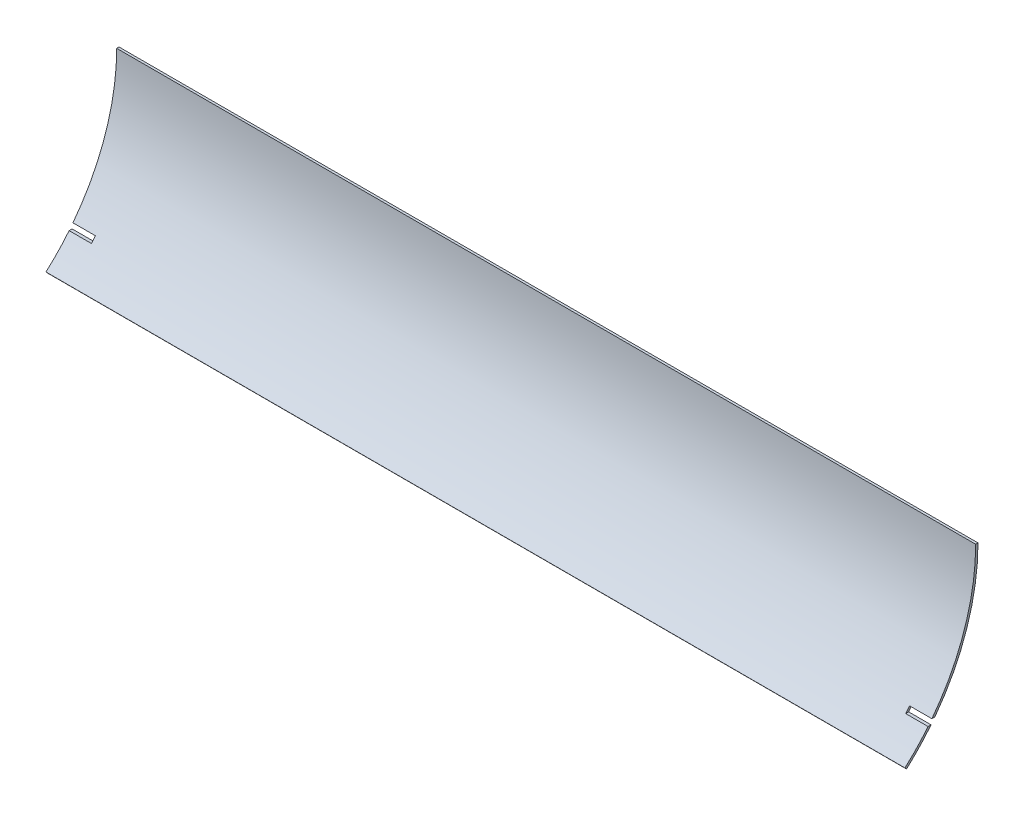
SolidWorks part; units mm, degrees
ref_plane "Front Plane" through (0, 0, 0) normal (0, 0, 1) x (1, 0, 0)
ref_plane "Top Plane" through (0, 0, 0) normal (0, 1, 0) x (1, 0, 0)
ref_plane "Right Plane" through (0, 0, 0) normal (1, 0, 0) x (0, 0, -1)
sketch "Sketch2" plane through (0, 0, 0) normal (1, 0, 0) x (0, 0, -1)
  arc A1 (97.053, -108.2878) -> (145.415, 0) centre (0, 0) ccw
  dimension "D1" = 145.415
extrude "Extrude-Thin1" add sketch "Sketch2" along normal blind 584.2 thin thin type mid plane wall 1.5875
sketch "Sketch3" plane through (0, 0, 0) normal (0, 0, 1) x (1, 0, 0)
  line L0 (0, -91.1867) -> (15.24, -91.1867)
  line L1 (0, 0) -> (0, -107.6967) construction
  line L2 (15.24, -91.1867) -> (15.24, -87.8847)
  line L3 (15.24, -87.8847) -> (0, -87.8847)
  line L4 (0, -87.8847) -> (0, -91.1867)
  line L5 (292.1, -107.6967) -> (292.1, 36.2793) construction
  line L6 (584.2, -107.6967) -> (0, -107.6967) construction
  line L7 (584.2, -87.8847) -> (584.2, -91.1867)
  line L8 (568.96, -87.8847) -> (584.2, -87.8847)
  line L9 (568.96, -91.1867) -> (568.96, -87.8847)
  line L10 (584.2, -91.1867) -> (568.96, -91.1867)
  dimension "D1" = 3.302
  dimension "D2" = 15.24
  dimension "D3" = 16.51
extrude "Cut-Extrude1" cut sketch "Sketch3" against normal through all
